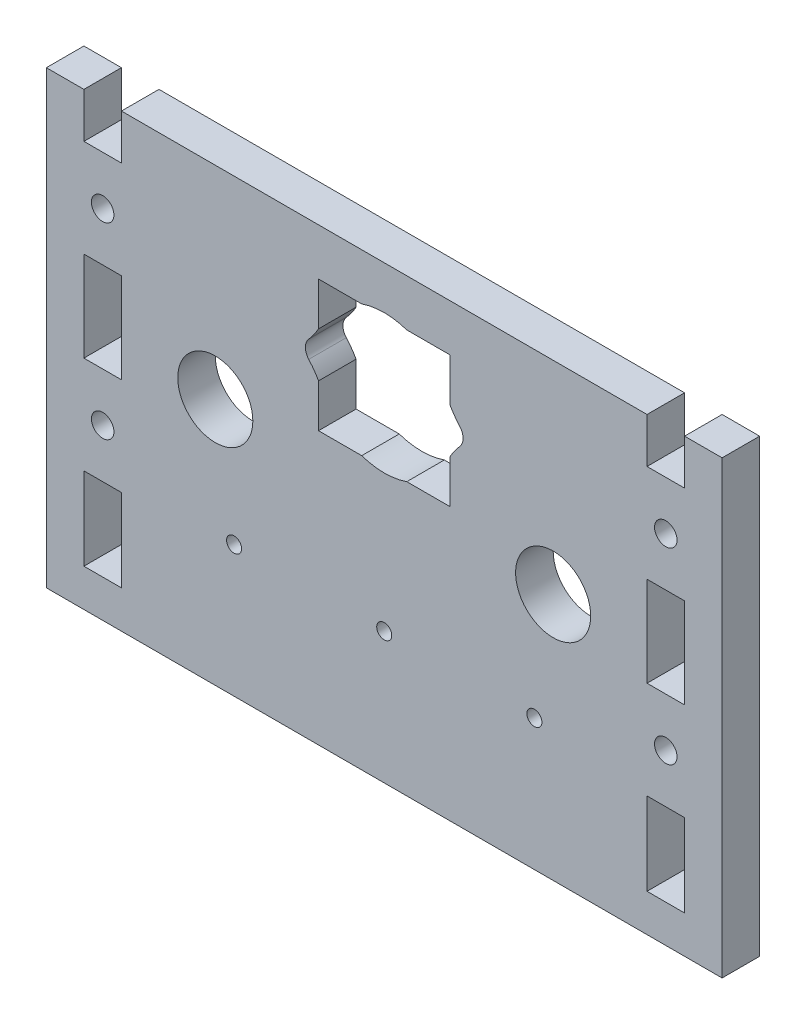
SolidWorks part; units mm, degrees
ref_plane "Front Plane" through (0, 0, 0) normal (0, 0, 1) x (1, 0, 0)
ref_plane "Top Plane" through (0, 0, 0) normal (0, 1, 0) x (1, 0, 0)
ref_plane "Right Plane" through (0, 0, 0) normal (1, 0, 0) x (0, 0, -1)
sketch "Sketch1" plane through (0, 0, 0) normal (0, 0, 1) x (1, 0, 0)
  line L0 (45, 30) -> (-45, -30) construction
  line L1 (-45, -30) -> (45, -30)
  line L2 (-45, -30) -> (-45, 30)
  line L3 (-45, 30) -> (45, 30)
  line L4 (45, -30) -> (45, 30)
  dimension "D1" = 60
  dimension "D2" = 90
extrude "Boss-Extrude1" add sketch "Sketch1" along normal blind 5
sketch "Sketch3" plane through (0, 0, 5) normal (0, 0, 1) x (1, 0, 0)
  line L0 (0, 15) -> (0, 0) construction
  line L1 (45, 30) -> (-45, 30) construction
  circle A0 centre (0, 15) radius 9.25
  dimension "D1" = 18.5
  dimension "D2" = 15
extrude "Cut-Extrude2" cut sketch "Sketch3" against normal blind 5
sketch "Sketch4" plane through (0, 0, 5) normal (0, 0, 1) x (1, 0, 0)
  line L1 (-8.75, 6.25) -> (8.75, 6.25)
  line L2 (-8.75, 6.25) -> (-8.75, 23.75)
  line L3 (-8.75, 23.75) -> (8.75, 23.75)
  line L4 (8.75, 6.25) -> (8.75, 23.75)
  line L5 (-8.75, 6.25) -> (8.75, 23.75) construction
  line L6 (-8.75, 23.75) -> (8.75, 6.25) construction
  point P0 (0, 15)
  dimension "D1" = 17.5
extrude "Cut-Extrude3" cut sketch "Sketch4" against normal blind 5
sketch "Sketch5" plane through (0, 0, 5) normal (0, 0, 1) x (1, 0, 0)
  line L0 (-8.75, 15) -> (8.75, 15) construction
  line L1 (0, 15) -> (0, 5.75) construction
  circle A0 centre (-8.75, 15) radius 1.75
  circle A1 centre (8.75, 15) radius 1.75
  arc A2 (-3, 6.25) -> (3, 6.25) centre (0, 15) ccw construction
  arc A3 (-8.75, 18) -> (-8.75, 12) centre (0, 15) ccw construction
  point P9 (-9.25, 15)
  dimension "D1" = 3.5
  dimension "D2" = 17.5
extrude "Cut-Extrude4" cut sketch "Sketch5" against normal blind 5
sketch "Sketch6" plane through (0, 0, 5) normal (0, 0, 1) x (1, 0, 0)
  line L0 (-20, -12.5) -> (20, -12.5) construction
  line L1 (-22.5, 3) -> (22.5, 3) construction
  line L2 (0, -12.5) -> (0, 0) construction
  line L3 (0, 0) -> (0, 3) construction
  circle A0 centre (-22.5, 3) radius 5
  circle A1 centre (22.5, 3) radius 5
  circle A2 centre (-20, -12.5) radius 1
  circle A3 centre (0, -12.5) radius 1
  circle A4 centre (20, -12.5) radius 1
  arc A5 (-3, 6.25) -> (3, 6.25) centre (0, 15) ccw construction
  point P10 (0, 15)
  dimension "D3" = 10
  dimension "D6" = 2
  dimension "D1" = 12
  dimension "D2" = 45
  dimension "D4" = 15.5
  dimension "D5" = 40
extrude "Cut-Extrude5" cut sketch "Sketch6" against normal blind 10
fillet "Fillet1" radius 10 4 edges at (9.0893, 13.2832, 2.5) (9.0893, 16.7168, 2.5) (-9.0893, 13.2832, 2.5) (-9.0893, 16.7168, 2.5)
sketch "Sketch7" plane through (0, 0, 5) normal (0, 0, 1) x (1, 0, 0)
  line L0 (-45, 30) -> (-45, -30) construction
  line L1 (-35, 35) -> (-40, 35)
  line L2 (-35, 35) -> (-35, -25)
  line L3 (-35, -25) -> (-40, -25)
  line L4 (-40, 35) -> (-40, -25)
  line L5 (-35, 35) -> (-40, -25) construction
  line L6 (-35, -25) -> (-40, 35) construction
  line L7 (-37.5, -7.5) -> (-37.5, 17.5) construction
  line L8 (-35, -1) -> (-40, -1)
  line L9 (-35, -1) -> (-35, -14)
  line L10 (-35, -14) -> (-40, -14)
  line L11 (-40, -1) -> (-40, -14)
  line L12 (-35, -1) -> (-40, -14) construction
  line L13 (-35, -14) -> (-40, -1) construction
  line L14 (-35, 24) -> (-40, 24)
  line L15 (-35, 24) -> (-35, 11)
  line L16 (-35, 11) -> (-40, 11)
  line L17 (-40, 24) -> (-40, 11)
  line L18 (-35, 24) -> (-40, 11) construction
  line L19 (-35, 11) -> (-40, 24) construction
  line L20 (45, 30) -> (-45, 30) construction
  circle A0 centre (-37.5, -7.5) radius 1.5
  circle A1 centre (-37.5, 17.5) radius 1.5
  point P0 (-37.5, 5)
  dimension "D6" = 3
  dimension "D1" = 5
  dimension "D2" = 5
  dimension "D3" = 25
  dimension "D4" = 13
  dimension "D5" = 13
  dimension "D7" = 11
  dimension "D8" = 25
extrude "Cut-Extrude6" cut sketch "Sketch7" against normal blind 5 contours L14 L2 L1 L4 | L2 L16 L4 L8 | L2 L10 L4 L3 | A1 | A0 region at (-37.5, 29.5, 5) region at (-37.5, 5, 5) region at (-37.5, -19.5, 5)
mirror "Mirror1" about plane through (0, 0, 0) normal (1, 0, 0) of "Cut-Extrude6"
